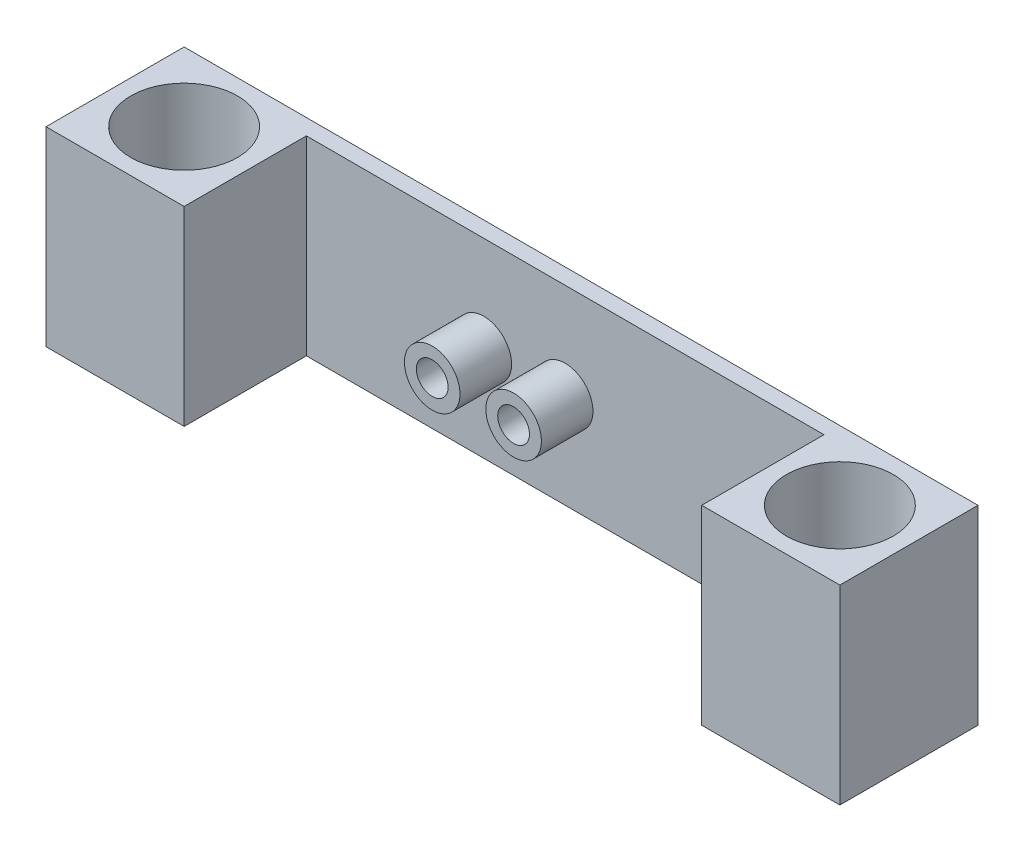
SolidWorks part; units mm, degrees
ref_plane "Front Plane" through (0, 0, 0) normal (0, 0, 1) x (1, 0, 0)
ref_plane "Top Plane" through (0, 0, 0) normal (0, 1, 0) x (1, 0, 0)
ref_plane "Right Plane" through (0, 0, 0) normal (1, 0, 0) x (0, 0, -1)
sketch "Sketch1" plane through (0, 0, 0) normal (0, 1, 0) x (1, 0, 0)
  line L1 (-17.4, 17.4) -> (17.4, 17.4)
  line L2 (-17.4, 13.4) -> (-17.4, -17.4)
  line L3 (-17.4, -17.4) -> (17.4, -17.4)
  line L4 (17.4, 17.4) -> (17.4, -17.4)
  line L5 (0, -17.4) -> (0, 17.4) construction
  line L6 (-17.4, 0) -> (17.4, 0) construction
  line L7 (-17.4, 17.4) -> (-82.6, 17.4)
  line L9 (-17.4, 13.4) -> (-82.6, 13.4)
  line L10 (-82.6, 17.4) -> (-82.6, 13.4)
  circle A0 centre (0, 0) radius 13.45
  dimension "D1" = 26.9
  dimension "D2" = 34.8
  dimension "D3" = 34.8
  dimension "D4" = 65.2
  dimension "D5" = 4
extrude "Boss-Extrude2" add sketch "Sketch1" along normal blind 48
mirror "Mirror2" about plane through (-82.6, 48, -17.4) normal (1, 0, 0) of "Boss-Extrude2"
sketch "Sketch7" plane through (0, 0, -13.4) normal (0, 0, 1) x (1, 0, 0)
  line L0 (-147.8, 24) -> (-17.4, 24) construction
  line L1 (-147.8, 48) -> (-147.8, 0) construction
  line L2 (-17.4, 48) -> (-17.4, 0) construction
  line L3 (-82.6, 48) -> (-82.6, 0) construction
  line L4 (-147.8, 48) -> (-17.4, 48) construction
  line L5 (-147.8, 0) -> (-17.4, 0) construction
  circle A0 centre (-82.6, 24) radius 4
  circle A1 centre (-82.6, 24) radius 7
  circle A2 centre (-103.1, 24) radius 4
  circle A3 centre (-103.1, 24) radius 7
  point P21 (0, 0)
  dimension "D1" = 8
  dimension "D3" = 8
  dimension "D5" = 20.5
  dimension "D2" = 3
  dimension "D4" = 3
extrude "Boss-Extrude3" add sketch "Sketch7" along normal blind 13
